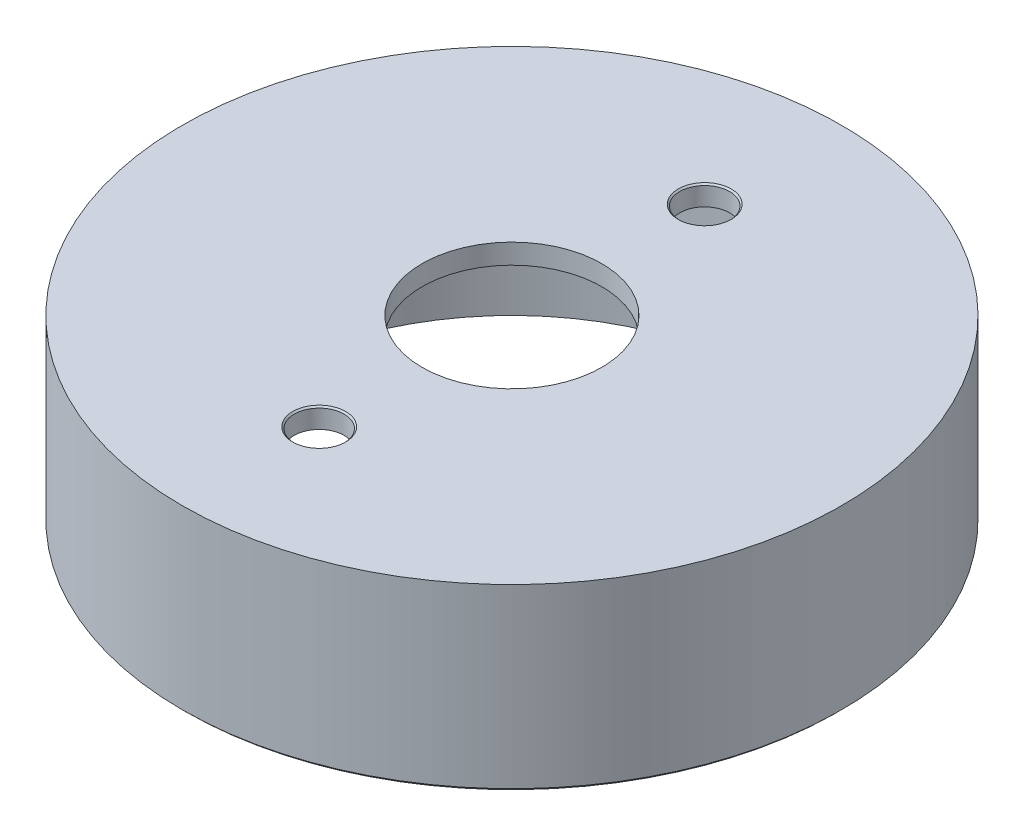
SolidWorks part; units mm, degrees
ref_plane "Front Plane" through (0, 0, 0) normal (0, 0, 1) x (1, 0, 0)
ref_plane "Top Plane" through (0, 0, 0) normal (0, 1, 0) x (1, 0, 0)
ref_plane "Right Plane" through (0, 0, 0) normal (1, 0, 0) x (0, 0, -1)
sketch "Sketch1" plane through (0, 0, 0) normal (0, 1, 0) x (1, 0, 0)
  circle A0 centre (0, 0) radius 12.73
  circle A1 centre (0, 0) radius 16.5
  dimension "D1" = 3.77
  dimension "D2" = 33
extrude "Boss-Extrude1" add sketch "Sketch1" along normal blind 8
sketch "Sketch2" plane through (0, 8, 0) normal (0, 1, 0) x (1, 0, 0)
  circle A0 centre (0, 0) radius 16.5
extrude "Boss-Extrude2" add sketch "Sketch2" along normal blind 1
sketch "Sketch3" plane through (0, 9, 0) normal (0, 1, 0) x (1, 0, 0)
  line L0 (0, 13) -> (0, 9.65)
  line L1 (0, -11.45) -> (0, -9.65)
  line L10 (0, 9.65) -> (0, 0)
  line L11 (0, 0) -> (0, -9.65)
  circle A0 centre (0, 0) radius 4.5
  circle A4 centre (0, 9.65) radius 1.25
  circle A5 centre (0, -9.65) radius 1.25
  dimension "D1" = 9
  dimension "D8" = 2.5
  dimension "D9" = 1.8
  dimension "D10" = 2.5
  dimension "D2" = 9.65
  dimension "D3" = 9.65
extrude "Cut-Extrude1" cut sketch "Sketch3" against normal blind 9.65 contours A0 | A4 | A5 | A0 | A4 | A5 region at (0.5305, 9, -9.65) region at (0.5305, 9, 9.65) region at (1.9099, 9, 0)
scale "Scale1" scale about centroid uniform scaling yes scale factor 1.666667
chamfer "Chamfer2" distance 0.125 angle 45 2 edges at (0, 11.6729, -14) (0, 11.6729, 18.1667)
chamfer "Chamfer4" distance 0.25 angle 45 1 edges at (0, -3.3271, 27.5)
